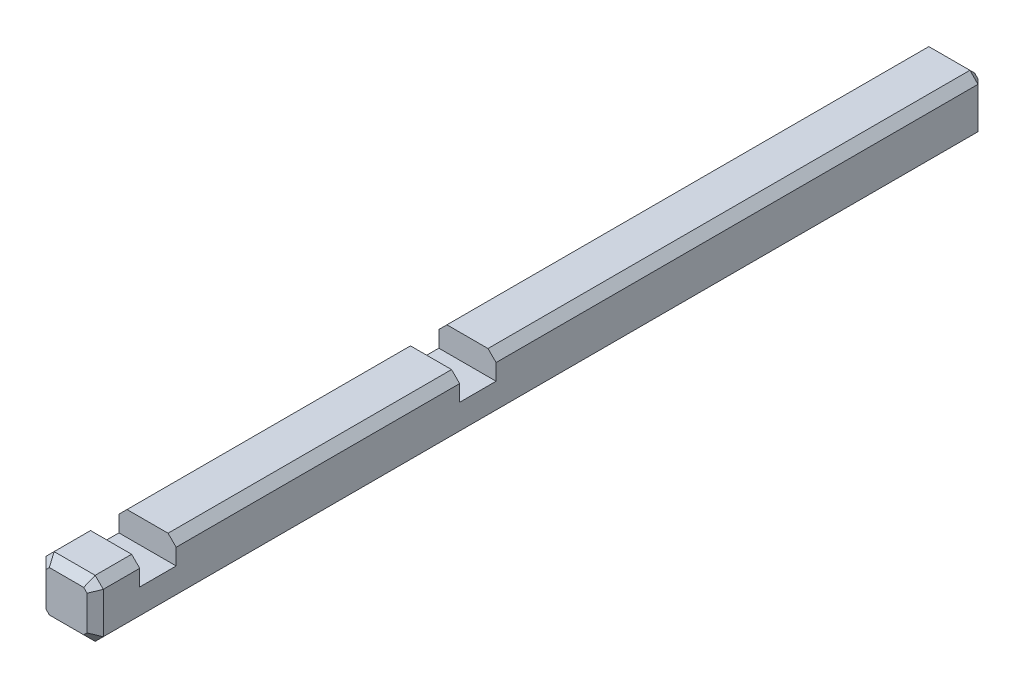
SolidWorks part; units mm, degrees
ref_plane "Front Plane" through (0, 0, 0) normal (0, 0, 1) x (1, 0, 0)
ref_plane "Top Plane" through (0, 0, 0) normal (0, 1, 0) x (1, 0, 0)
ref_plane "Right Plane" through (0, 0, 0) normal (1, 0, 0) x (0, 0, -1)
sketch "Sketch1" plane through (0, 0, 0) normal (0, 0, 1) x (1, 0, 0)
  line L1 (3.5355, -3.5355) -> (-3.5355, -3.5355)
  line L2 (3.5355, -3.5355) -> (3.5355, 3.5355)
  line L3 (3.5355, 3.5355) -> (-3.5355, 3.5355)
  line L4 (-3.5355, -3.5355) -> (-3.5355, 3.5355)
  line L5 (3.5355, -3.5355) -> (-3.5355, 3.5355) construction
  line L6 (3.5355, 3.5355) -> (-3.5355, -3.5355) construction
  circle A0 centre (0, 0) radius 5 construction
  dimension "D1" = 10
extrude "Boss-Extrude1" add sketch "Sketch1" along normal blind 110
chamfer "Chamfer2" distance 1 angle 45 4 edges at (3.5355, -3.5355, 55) (-3.5355, -3.5355, 55) (3.5355, 3.5355, 55) (-3.5355, 3.5355, 55)
sketch "Sketch2" plane through (0, 0, 0) normal (0, 1, 0) x (1, 0, 0)
  line L0 (2.5355, -110) -> (-2.5355, -110) construction
  point P0 (0, -65)
  point P3 (0, -110)
  point P4 (0, 0)
  point P5 (0, -104.5)
  dimension "D1" = 45
  dimension "D2" = 5.5
ref_plane "Plane1" through (0, 0, 65) normal (0, 0, -1) x (-1, 0, 0)
sketch "Sketch3" plane through (0, 0, 65) normal (0, 0, -1) x (-1, 0, 0)
  line L0 (-3.5355, -2.5355) -> (-3.5355, 2.5355) construction
  line L1 (-3.5355, 0.5355) -> (3.5355, 0.5355)
  line L2 (-3.5355, 0.5355) -> (-3.5355, 3.5355)
  line L3 (-3.5355, 3.5355) -> (3.5355, 3.5355)
  line L4 (3.5355, 0.5355) -> (3.5355, 3.5355)
  line L5 (3.5355, 2.5355) -> (3.5355, -2.5355) construction
  line L6 (-2.5355, 3.5355) -> (2.5355, 3.5355) construction
  dimension "D1" = 3
extrude "Cut-Extrude1" cut sketch "Sketch3" along normal blind 4.5
ref_plane "Plane2" through (0, 0, 104.5) normal (0, 0, -1) x (-1, 0, 0)
sketch "Sketch4" plane through (0, 0, 104.5) normal (0, 0, -1) x (-1, 0, 0)
  line L0 (-3.5355, -2.5355) -> (-3.5355, 2.5355) construction
  line L1 (-3.5355, 0.5355) -> (3.5355, 0.5355)
  line L2 (-3.5355, 0.5355) -> (-3.5355, 3.5355)
  line L3 (-3.5355, 3.5355) -> (3.5355, 3.5355)
  line L4 (3.5355, 0.5355) -> (3.5355, 3.5355)
  line L5 (3.5355, 2.5355) -> (3.5355, -2.5355) construction
  line L6 (-2.5355, 3.5355) -> (2.5355, 3.5355) construction
  dimension "D1" = 3
extrude "Cut-Extrude2" cut sketch "Sketch4" along normal blind 4.5
chamfer "Chamfer3" distance 1 angle 45 16 edges at (3.0355, 3.0355, 0) (0, 3.5355, 0) (-3.0355, 3.0355, 0) (-3.5355, 0, 0) (-3.0355, -3.0355, 0) (0, -3.5355, 0) (3.0355, -3.0355, 0) (3.5355, 0, 0) (-3.0355, -3.0355, 110) (-3.5355, 0, 110) (-3.0355, 3.0355, 110) (0, 3.5355, 110) (3.0355, 3.0355, 110) (3.5355, 0, 110) (3.0355, -3.0355, 110) (0, -3.5355, 110)
equation "\"thiccness\"=4.5"
equation "\"D1@Cut-Extrude1\"=\"thiccness\""
equation "\"cut\"=3"
equation "\"D1@Sketch4\"=\"cut\""
equation "\"D1@Cut-Extrude2\"=\"thiccness\""
equation "\"D1@Sketch3\"=\"cut\""
